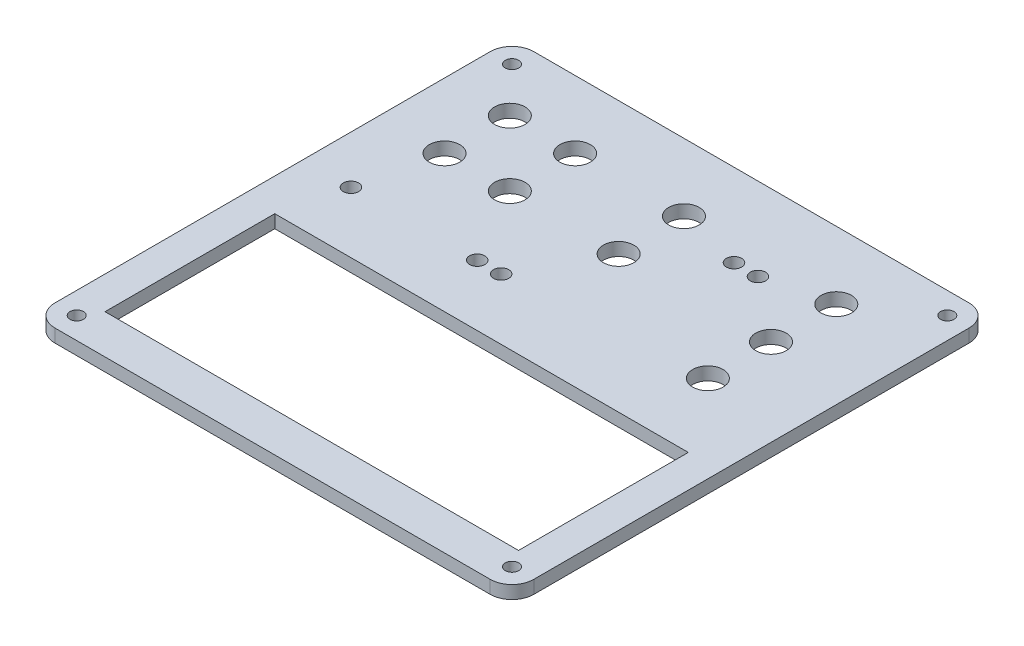
SolidWorks part; units mm, degrees
ref_plane "Front Plane" through (0, 0, 0) normal (0, 0, 1) x (1, 0, 0)
ref_plane "Top Plane" through (0, 0, 0) normal (0, 1, 0) x (1, 0, 0)
ref_plane "Right Plane" through (0, 0, 0) normal (1, 0, 0) x (0, 0, -1)
sketch "Sketch1" plane through (0, 0, 0) normal (0, 1, 0) x (1, 0, 0)
  line L1 (-55, 55) -> (55, 55)
  line L2 (-55, 55) -> (-55, -55)
  line L3 (-55, -55) -> (55, -55)
  line L4 (55, 55) -> (55, -55)
  line L5 (-55, 55) -> (55, -55) construction
  line L6 (-55, -55) -> (55, 55) construction
  circle A0 centre (-50, 50) radius 1.55
  circle A1 centre (50, 50) radius 1.55
  circle A2 centre (50, -50) radius 1.55
  circle A3 centre (-50, -50) radius 1.55
  point P0 (0, 0)
  dimension "D4" = 3.1
  dimension "D8" = 3.1
  dimension "D9" = 3.1
  dimension "D10" = 3.1
  dimension "D1" = 110
  dimension "D2" = 110
  dimension "D3" = 5
  dimension "D5" = 5
  dimension "D6" = 5
  dimension "D7" = 5
extrude "Boss-Extrude1" add sketch "Sketch1" along normal blind 3 contours A3 | A2 | A1 | A0 | L1 L4 L3 L2
fillet "Fillet1" radius 5 4 edges at (-55, 1.5, -55) (55, 1.5, -55) (55, 1.5, 55) (-55, 1.5, 55)
sketch "Sketch2" plane through (0, 3, 0) normal (0, 1, 0) x (1, 0, 0)
  line L0 (0, 55) -> (0, -55) construction
  line L1 (-47.5, -46) -> (47.5, -46)
  line L2 (-47.5, -46) -> (-47.5, -7)
  line L3 (-47.5, -7) -> (47.5, -7)
  line L4 (47.5, -46) -> (47.5, -7)
  line L5 (-50, 55) -> (50, 55) construction
  line L6 (-50, -55) -> (50, -55) construction
  line L7 (-55, 50) -> (-55, -50) construction
  line L8 (55, 50) -> (55, -50) construction
  dimension "D1" = 7.5
  dimension "D2" = 7.5
  dimension "D3" = 39
  dimension "D4" = 9
extrude "Cut-Extrude1" cut sketch "Sketch2" against normal through all contours L3 L4 L1 L2
sketch "Sketch3" plane through (0, 3, 0) normal (0, 1, 0) x (1, 0, 0)
  line L0 (35, 55) -> (35, -55) construction
  line L1 (-55, 50) -> (-55, -50) construction
  line L2 (-55, 39.5) -> (55, 39.5) construction
  line L3 (55, 50) -> (55, -50) construction
  line L4 (-55, 24.5) -> (55, 24.5) construction
  line L5 (-55, 9.5) -> (55, 9.5) construction
  line L6 (-40, 55) -> (-40, -55) construction
  line L7 (-50, 55) -> (50, 55) construction
  line L8 (-50, -55) -> (50, -55) construction
  line L9 (-25, 55) -> (-25, -55) construction
  line L10 (0, 55) -> (0, -55) construction
  circle A0 centre (-40, 39.5) radius 3.5
  circle A1 centre (-40, 24.5) radius 3.5
  circle A3 centre (-25, 39.5) radius 3.5
  circle A4 centre (-25, 24.5) radius 3.5
  circle A5 centre (0, 39.5) radius 3.5
  circle A6 centre (0, 24.5) radius 3.5
  circle A7 centre (35, 39.5) radius 3.5
  circle A8 centre (35, 24.5) radius 3.5
  circle A9 centre (35, 10) radius 3.5
  dimension "D3" = 7
  dimension "D4" = 7
  dimension "D5" = 7
  dimension "D8" = 7
  dimension "D9" = 15
  dimension "D11" = 7
  dimension "D12" = 7
  dimension "D13" = 7
  dimension "D15" = 7
  dimension "D16" = 7
  dimension "D1" = 15
  dimension "D2" = 15.5
  dimension "D6" = 15
  dimension "D7" = 15
  dimension "D10" = 25
  dimension "D14" = 35
extrude "Cut-Extrude2" cut sketch "Sketch3" against normal through all contours A1 | A3 | A4 | A5 | A6 | A0 | A7 | A8 | A9 region at (-40, 3, -24.5) region at (-25, 3, -39.5) region at (-25, 3, -24.5) region at (0, 3, -39.5) region at (0, 3, -24.5)
sketch "Sketch4" plane through (0, 3, 0) normal (0, 1, 0) x (1, 0, 0)
  line L1 (-55, 50) -> (-55, -50) construction
  line L2 (55, 50) -> (55, -50) construction
  line L3 (-44, -55) -> (-44, 55) construction
  line L4 (-50, -55) -> (50, -55) construction
  line L5 (-50, 55) -> (50, 55) construction
  line L6 (-15, 55) -> (-15, -55) construction
  line L7 (-55, 7) -> (55, 7) construction
  line L8 (-55, 36) -> (55, 36) construction
  line L9 (15, 55) -> (15, -55) construction
  circle A0 centre (-44, 7) radius 1.75
  circle A1 centre (-15, 7) radius 1.75
  circle A2 centre (-9.5, 7) radius 1.75
  circle A3 centre (15, 36) radius 1.75
  circle A4 centre (20.5, 36) radius 1.75
  dimension "D3" = 3.5
  dimension "D4" = 40
  dimension "D6" = 3.5
  dimension "D8" = 3.5
  dimension "D9" = 3.5
  dimension "D10" = 3.5
  dimension "D1" = 11
  dimension "D5" = 62
  dimension "D7" = 5.5
  dimension "D11" = 5.5
  dimension "D12" = 40
  dimension "D13" = 19
extrude "Cut-Extrude3" cut sketch "Sketch4" against normal through all contours A0 | A1 | A2 | A3 | A4
